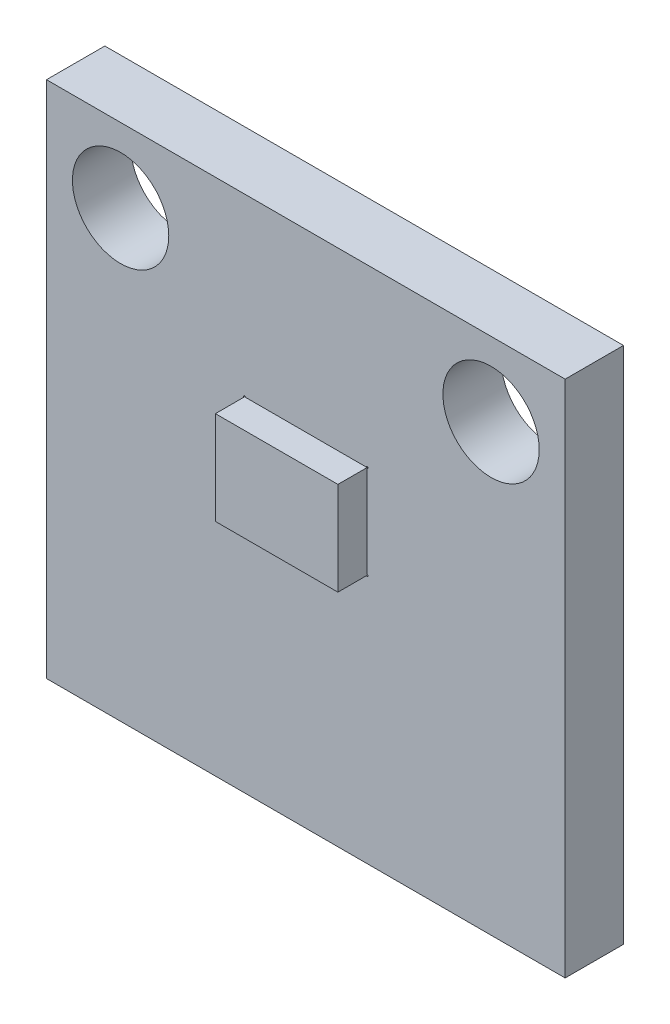
SolidWorks part; units mm, degrees
ref_plane "Front Plane" through (0, 0, 0) normal (0, 0, 1) x (1, 0, 0)
ref_plane "Top Plane" through (0, 0, 0) normal (0, 1, 0) x (1, 0, 0)
ref_plane "Right Plane" through (0, 0, 0) normal (1, 0, 0) x (0, 0, -1)
sketch "Model" plane through (0, 0, 0) normal (0, 0, 1) x (1, 0, 0)
  line L0 (0, 0) -> (0, 17.78)
  line L1 (0, 17.78) -> (17.78, 17.78)
  line L2 (17.78, 17.78) -> (17.78, 0)
  line L3 (17.78, 0) -> (0, 0)
  line L247 (6.79, 8.56) -> (10.99, 8.56)
  line L248 (6.79, 11.76) -> (6.79, 8.56)
  line L249 (10.99, 11.76) -> (6.79, 11.76)
  line L250 (10.99, 8.56) -> (10.99, 11.76)
  circle A0 centre (2.54, 15.24) radius 1.651
  circle A1 centre (15.24, 15.24) radius 1.651
  arc A2 (0.0508, 17.78) -> (-0.0508, 17.78) centre (0, 17.78) ccw
  arc A3 (-0.0508, 0) -> (0.0508, 0) centre (0, 0) ccw
  arc A4 (17.78, 17.7292) -> (17.78, 17.8308) centre (17.78, 17.78) ccw
  arc A5 (0, 17.8308) -> (0, 17.7292) centre (0, 17.78) ccw
  arc A6 (17.7292, 0) -> (17.8308, 0) centre (17.78, 0) ccw
  arc A7 (17.8308, 17.78) -> (17.7292, 17.78) centre (17.78, 17.78) ccw
  arc A8 (0, 0.0508) -> (0, -0.0508) centre (0, 0) ccw
  arc A9 (17.78, -0.0508) -> (17.78, 0.0508) centre (17.78, 0) ccw
  arc A496 (10.99, 8.5283) -> (10.99, 8.5918) centre (10.99, 8.56) ccw
  arc A497 (6.79, 8.5918) -> (6.79, 8.5283) centre (6.79, 8.56) ccw
  arc A498 (6.7583, 8.56) -> (6.8218, 8.56) centre (6.79, 8.56) ccw
  arc A499 (6.8218, 11.76) -> (6.7583, 11.76) centre (6.79, 11.76) ccw
  arc A500 (6.79, 11.7917) -> (6.79, 11.7282) centre (6.79, 11.76) ccw
  arc A501 (10.99, 11.7282) -> (10.99, 11.7917) centre (10.99, 11.76) ccw
  arc A502 (11.0217, 11.76) -> (10.9582, 11.76) centre (10.99, 11.76) ccw
  arc A503 (10.9582, 8.56) -> (11.0217, 8.56) centre (10.99, 8.56) ccw
extrude "Boss-Extrude1" add sketch "Model" along normal blind 2 contours L3 L2 L1 L0 A503 L247 A498 A497 L248 A500 A499 L249 A502 A501 L250 A496 A1 A0 | L247 L250 L249 L248 region at (8.89, 8.4493, 0) region at (8.89, 10.16, 0)
extrude "Boss-Extrude2" add sketch "Model<3>" along normal blind 3 contours L247 L250 L249 L248 region at (8.89, 10.16, 0)
sketch "Model<3>" plane through (0, 0, 0) normal (0, 0, 1) x (1, 0, 0) same geometry as "Model"
